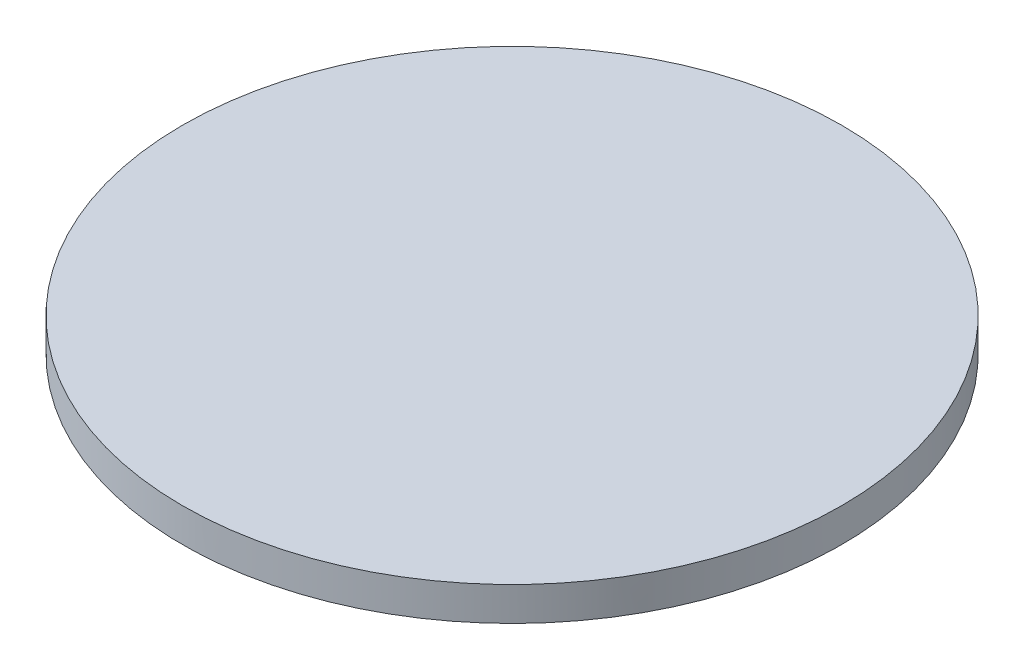
SolidWorks part; units mm, degrees
material "1060 Alloy"
ref_plane "Front Plane" through (0, 0, 0) normal (0, 0, 1) x (1, 0, 0)
ref_plane "Top Plane" through (0, 0, 0) normal (0, 1, 0) x (1, 0, 0)
ref_plane "Right Plane" through (0, 0, 0) normal (1, 0, 0) x (0, 0, -1)
sketch "Sketch1" plane through (0, 0, 0) normal (0, 1, 0) x (1, 0, 0)
  circle A0 centre (0, 0) radius 19.53
  dimension "D1" = 39.06
extrude "Boss-Extrude1" add sketch "Sketch1" along normal blind 1
sketch "Sketch2" plane through (0, 0, 0) normal (0, -1, 0) x (1, 0, 0)
  circle A0 centre (0, 0) radius 19.53
  circle A1 centre (0, 0) radius 18.53
  circle A2 centre (0, 0) radius 19.53 construction
  dimension "D1" = 0
  dimension "D2" = 37.06
extrude "Boss-Extrude2" add sketch "Sketch2" along normal blind 1
thread "Thread1" pitch 0.25 method cut profile "Thread Profile1" start angle 0, offset 0, length 1, pitch 0.25, diameter 37.06
ref_plane "Plane1" through (18.53, -1, 0) normal (0, 0, 1) x (1, 0, 0)
sketch "Thread Profile1" plane through (18.53, -1, 0) normal (0, 0, 1) x (1, 0, 0)
  line L0 (0, 0) -> (0, 0.25) construction
  line L1 (0, 0) -> (0.1353, 0.0781)
  line L2 (0.1353, 0.0781) -> (0.1353, 0.1094)
  line L3 (0.1353, 0.1094) -> (0, 0.1875)
  line L4 (0.1353, 0.0937) -> (0, 0.0937) construction
  line L11 (0, 0) -> (0, 0.1875)
  point P2 (0, 0)
  dimension "Pitch" = 0.25
  dimension "Profile_Angle" = 60
  dimension "Profile_Land" = 0.0312
  dimension "Profile_Height" = 0.1353
sketch "Sketch3" plane through (0, 0, 0) normal (0, -1, 0) x (1, 0, 0)
  circle A0 centre (0, 0) radius 15.03
  circle A1 centre (0, 0) radius 12.8689
  dimension "D1" = 30.06
extrude "Boss-Extrude3" add sketch "Sketch3" along normal blind 1
